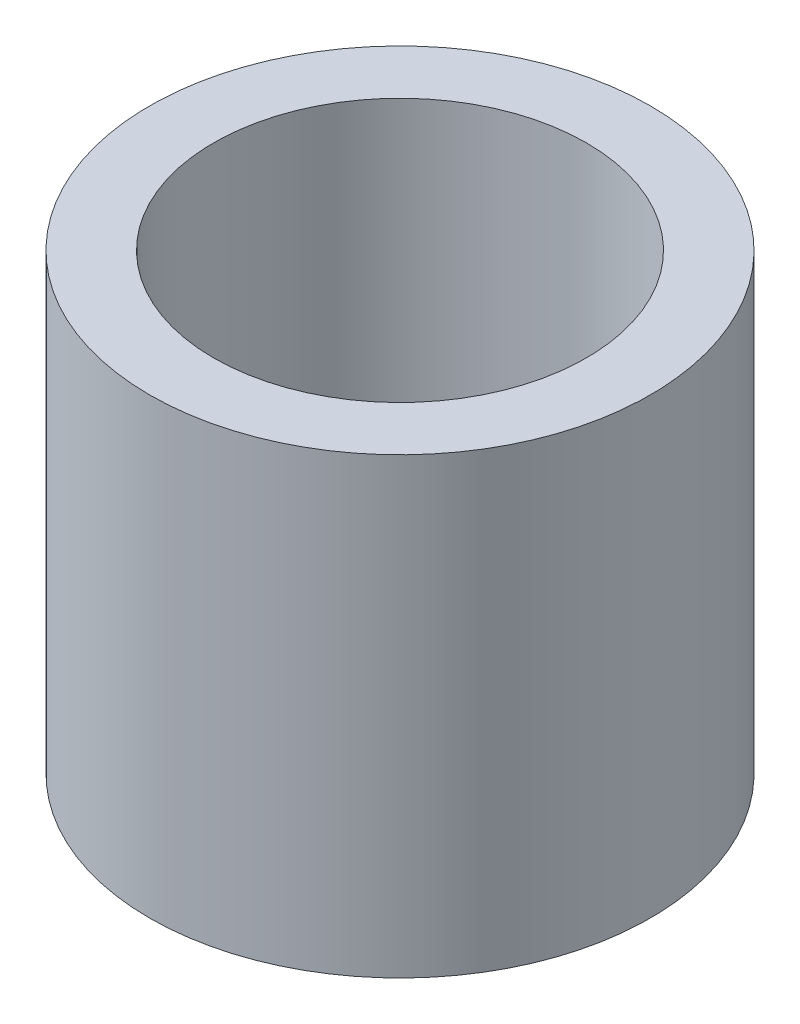
SolidWorks part; units mm, degrees
material "Copper"
ref_plane "Front Plane" through (0, 0, 0) normal (0, 0, 1) x (1, 0, 0)
ref_plane "Top Plane" through (0, 0, 0) normal (0, 1, 0) x (1, 0, 0)
ref_plane "Right Plane" through (0, 0, 0) normal (1, 0, 0) x (0, 0, -1)
sketch "Sketch1" plane through (0, 0, 0) normal (0, 0, 1) x (1, 0, 0)
  line L0 (0, 0) -> (1.645, 0) construction
  line L1 (1.645, 0) -> (2.21, 0)
  line L2 (1.645, 0) -> (1.645, 4)
  line L3 (1.645, 4) -> (2.21, 4)
  line L4 (2.21, 0) -> (2.21, 4)
  line L5 (0, 0) -> (0, 7.7064) construction
  dimension "D1" = 4
  dimension "D2" = 4.42
  dimension "D3" = 3.29
revolve "Revolve1" add sketch "Sketch1" angle 360 about L5
